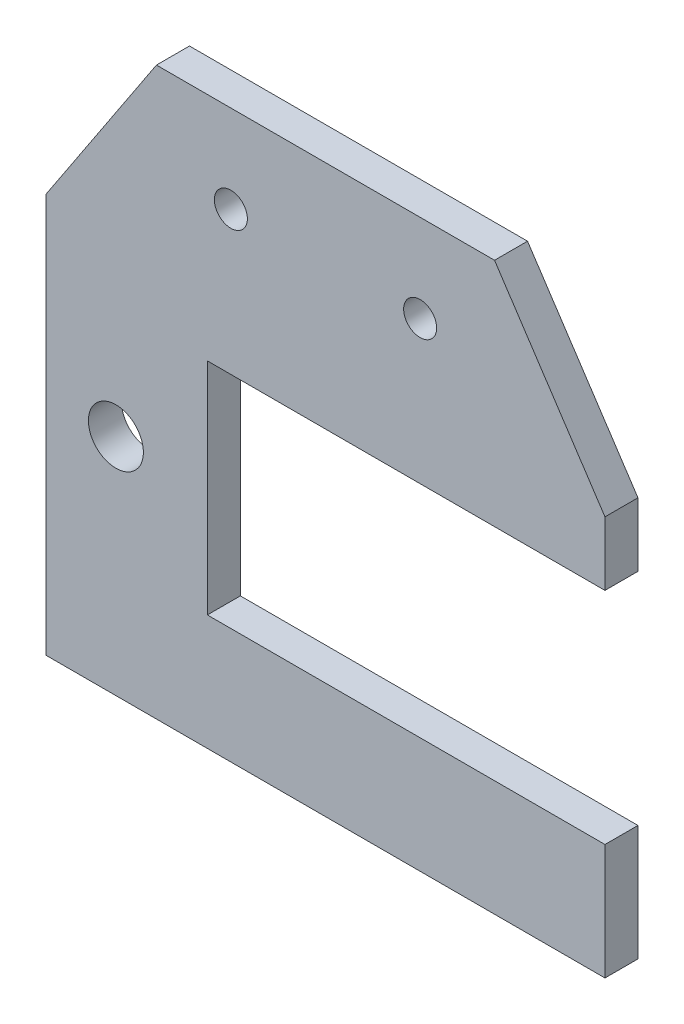
SolidWorks part; units mm, degrees
material "Plain Carbon Steel"
ref_plane "Front Plane" through (0, 0, 0) normal (0, 0, 1) x (1, 0, 0)
ref_plane "Top Plane" through (0, 0, 0) normal (0, 1, 0) x (1, 0, 0)
ref_plane "Right Plane" through (0, 0, 0) normal (1, 0, 0) x (0, 0, -1)
sketch "Sketch1" plane through (0, 0, 0) normal (0, 0, 1) x (1, 0, 0)
  line L0 (0, -12.3213) -> (0, 39.1607)
  line L1 (15.365, 39.1607) -> (-15.365, 39.1607)
  line L2 (-15.365, 39.1607) -> (-25.4023, 23.9787)
  line L3 (-25.4023, 23.9787) -> (-25.4023, -12.3213)
  line L4 (-25.4023, -12.3213) -> (25.4023, -12.3213)
  line L5 (25.4023, 23.9787) -> (25.4023, -12.3213)
  line L6 (15.365, 39.1607) -> (25.4023, 23.9787)
  line L8 (-10.7377, 18.1887) -> (25.4023, 18.1887)
  line L9 (-10.7377, 18.1887) -> (-10.7377, -1.8113)
  line L10 (-10.7377, -1.8113) -> (25.4023, -1.8113)
  line L11 (25.4023, 18.1887) -> (25.4023, -1.8113)
  line L12 (-10.7377, 18.1887) -> (25.4023, -1.8113) construction
  line L13 (-10.7377, -1.8113) -> (25.4023, 18.1887) construction
  circle A0 centre (-19.0523, 8.0787) radius 2.5
  circle A1 centre (-8.6023, 31.1907) radius 1.5
  circle A2 centre (8.6023, 31.1907) radius 1.5
  point P9 (7.3323, 8.1887)
  dimension "D8" = 3
  dimension "D9" = 3
  dimension "D10" = 5
  dimension "D11" = 6.35
  dimension "D12" = 20.4
  dimension "D13" = 7.97
  dimension "D14" = 3
  dimension "D15" = 7.97
  dimension "D16" = 16.8
  dimension "D17" = 16.8
  dimension "D1" = 213.47
  dimension "D2" = 36.3
  dimension "D3" = 18.2
  dimension "D4" = 30.73
  dimension "D5" = 10.51
  dimension "D6" = 20
  dimension "D7" = 36.14
extrude "Boss-Extrude1" add sketch "Sketch1" along normal blind 3 contours L10 L9 L8 L0 L1 L2 L3 L4 A1 A0 | L0 L8 L5 L6 L1 A2 | L10 L0 L4 L5 region at (-13.4749, 12.9419, 0) region at (12.7012, -7.0663, 0) region at (11.1797, 27.7155, 0)
